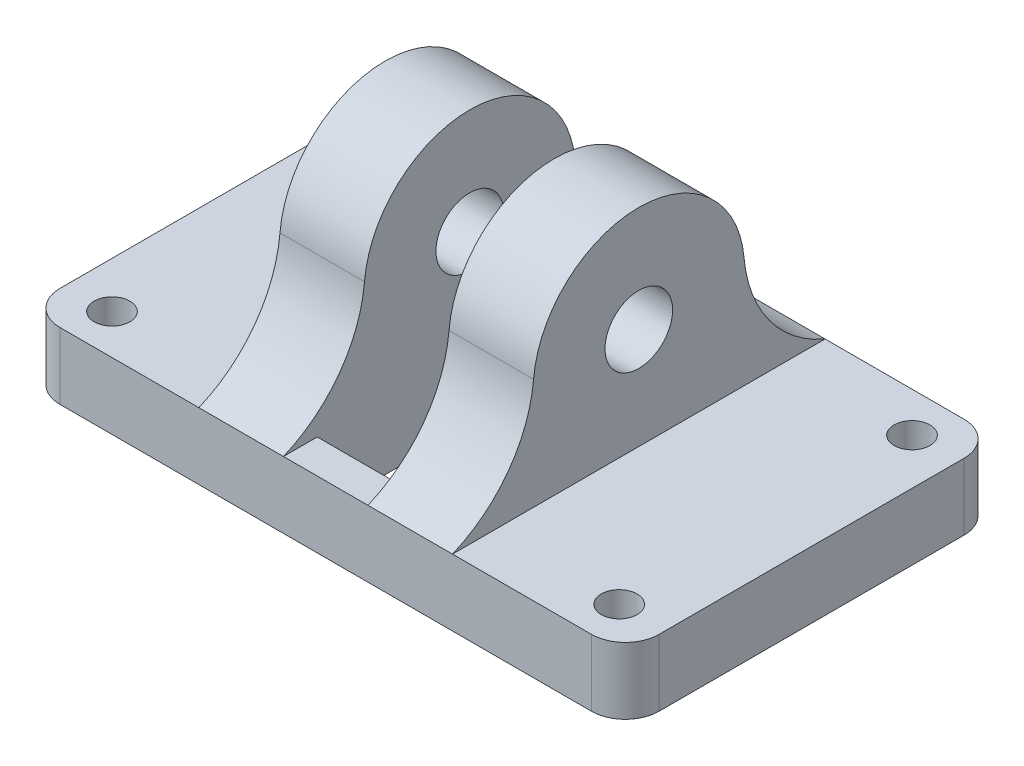
SolidWorks part; units mm, degrees
material "ABS PC"
ref_plane "Front Plane" through (0, 0, 0) normal (0, 0, 1) x (1, 0, 0)
ref_plane "Top Plane" through (0, 0, 0) normal (0, 1, 0) x (1, 0, 0)
ref_plane "Right Plane" through (0, 0, 0) normal (1, 0, 0) x (0, 0, -1)
sketch "Sketch1" plane through (0, 0, 0) normal (0, 1, 0) x (1, 0, 0)
  line L1 (0, 0) -> (45.0088, 0)
  line L2 (0, 0) -> (0, 27.9908)
  line L3 (0, 27.9908) -> (45.0088, 27.9908)
  line L4 (45.0088, 0) -> (45.0088, 27.9908)
  dimension "D1" = 27.9908
  dimension "D2" = 45.0088
extrude "Boss-Extrude1" add sketch "Sketch1" along normal blind 5.0038
sketch "Sketch2" plane through (0, 5.0038, 0) normal (0, 1, 0) x (1, 0, 0)
  line L8 (22.5044, 0) -> (22.5044, 27.9908) construction
  line L9 (0, 0) -> (45.0088, 0) construction
  line L10 (45.0088, 27.9908) -> (0, 27.9908) construction
  line L13 (45.0088, 13.9954) -> (0, 13.9954) construction
  line L16 (45.0088, 0) -> (45.0088, 27.9908) construction
  line L17 (0, 27.9908) -> (0, 0) construction
  circle A0 centre (41.5544, 24.9936) radius 1.3462
  circle A1 centre (41.5544, 2.9972) radius 1.3462
  circle A2 centre (3.4544, 24.9936) radius 1.3462
  circle A3 centre (3.4544, 2.9972) radius 1.3462
  point P25 (22.5044, 13.9954)
  point P26 (22.5044, 13.9954)
  point P27 (22.5044, 13.9954)
  dimension "D1" = 2.6924
  dimension "D2" = 19.05
  dimension "D3" = 10.9982
extrude "Cut-Extrude1" cut sketch "Sketch2" against normal blind 5.0038
fillet "Fillet1" radius 2.54 4 edges at (0, 2.5019, 0) (0, 2.5019, -27.9908) (45.0088, 2.5019, -27.9908) (45.0088, 2.5019, 0)
ref_plane "Plane1" through (22.5044, 0, 0) normal (1, 0, 0) x (0, 0, -1)
sketch "Sketch3" plane through (22.5044, 0, 0) normal (1, 0, 0) x (0, 0, -1)
  line L0 (2.54, 5.0038) -> (25.4508, 5.0038) construction
  circle A0 centre (13.9954, 12.6238) radius 7.9375
  circle A1 centre (13.9954, 12.6238) radius 2.54
  dimension "D1" = 15.875
  dimension "D3" = 5.08
  dimension "D2" = 7.62
extrude "Boss-Extrude2" add sketch "Sketch3" along normal blind 6.35 from offset 3.175
sketch "Sketch4" plane through (22.5044, 0, 0) normal (1, 0, 0) x (0, 0, -1)
  circle A0 centre (13.9954, 12.6238) radius 7.9375
  circle A1 centre (13.9954, 12.6238) radius 2.54
extrude "Boss-Extrude3" add sketch "Sketch4" against normal blind 6.35 from offset 3.175 offset against normal yes
fillet "Fillet2" radius 10 4 edges at (28.8544, 5.0038, -11.7729) (28.8544, 5.0038, -16.2179) (16.1544, 5.0038, -16.2179) (16.1544, 5.0038, -11.7729)
sketch "Sketch5" plane through (0, 5.0038, 0) normal (0, 1, 0) x (1, 0, 0)
  line L0 (25.6794, 27.9908) -> (25.6794, 0) construction
  line L1 (25.6794, 2.54) -> (19.3294, 2.54)
  line L2 (25.6794, 2.54) -> (25.6794, 25.4508)
  line L3 (25.6794, 25.4508) -> (19.3294, 25.4508)
  line L4 (19.3294, 2.54) -> (19.3294, 25.4508)
  line L5 (19.3294, 27.9908) -> (19.3294, 0) construction
  line L6 (19.3294, 0) -> (25.6794, 0) construction
  line L7 (25.6794, 27.9908) -> (19.3294, 27.9908) construction
  dimension "D1" = 2.54
  dimension "D2" = 2.54
extrude "Cut-Extrude2" cut sketch "Sketch5" against normal through all
